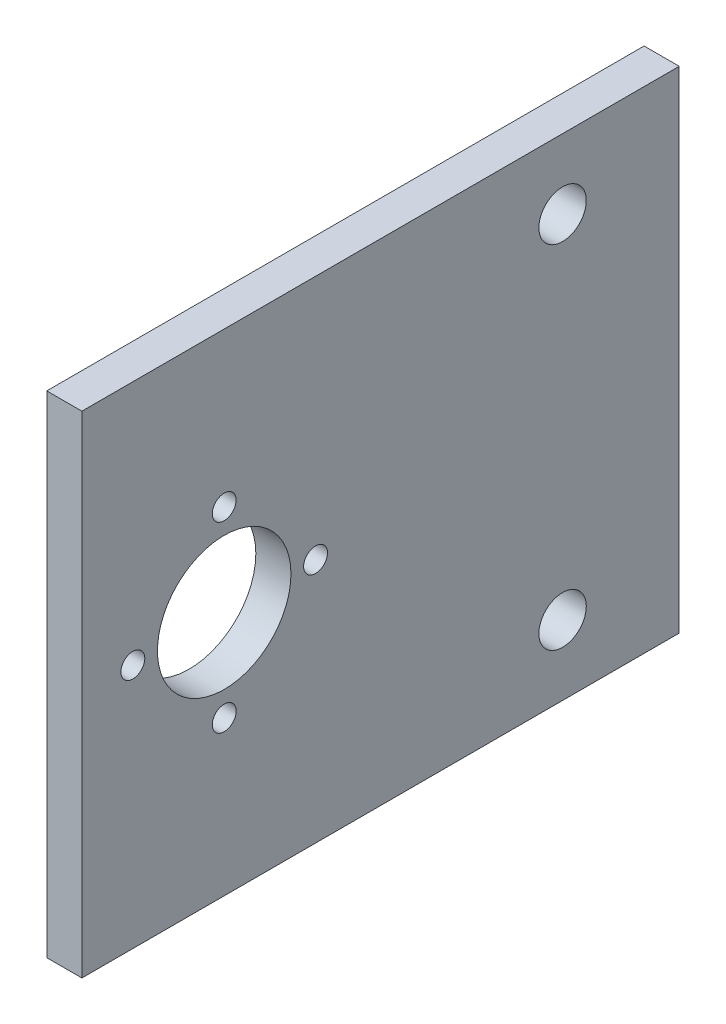
SolidWorks part; units mm, degrees
ref_plane "Front Plane" through (0, 0, 0) normal (1, 0, 0) x (0, 1, 0)
ref_plane "Top Plane" through (0, 0, 0) normal (0, 0, 1) x (0, 1, 0)
ref_plane "Right Plane" through (0, 0, 0) normal (0, 1, 0) x (-1, 0, 0)
sketch "Sketch1" plane through (0, 0, 0) normal (1, 0, 0) x (0, 1, 0)
  line L0 (-34.925, 22.25) -> (34.925, 22.25) construction
  line L1 (-34.925, -42.5) -> (34.925, -42.5)
  line L2 (-34.925, -42.5) -> (-34.925, 42.5)
  line L3 (-34.925, 42.5) -> (34.925, 42.5)
  line L4 (34.925, -42.5) -> (34.925, 42.5)
  line L5 (-34.925, -42.5) -> (34.925, 42.5) construction
  line L6 (-34.925, 42.5) -> (34.925, -42.5) construction
  line L7 (0, 42.5) -> (0, -42.5) construction
  line L8 (-34.925, -25.9) -> (34.925, -25.9) construction
  circle A1 centre (0, 35.25) radius 1.7
  circle A2 centre (0, 9.25) radius 1.7
  circle A3 centre (-13, 22.25) radius 1.7
  circle A4 centre (13, 22.25) radius 1.7
  circle A5 centre (0, 22.25) radius 9.5
  circle A6 centre (-25, -25.9) radius 3.3731
  circle A7 centre (25, -25.9) radius 3.3731
  point P0 (0, 0)
  dimension "D5" = 13
  dimension "D4" = 3.4
  dimension "D8" = 19
  dimension "D10" = 6.7462
  dimension "D1" = 85
  dimension "D2" = 69.85
  dimension "D3" = 64.75
  dimension "D7" = 13
  dimension "D9" = 16.6
  dimension "D11" = 25
extrude "Boss-Extrude1" add sketch "Sketch1" along normal blind 5
